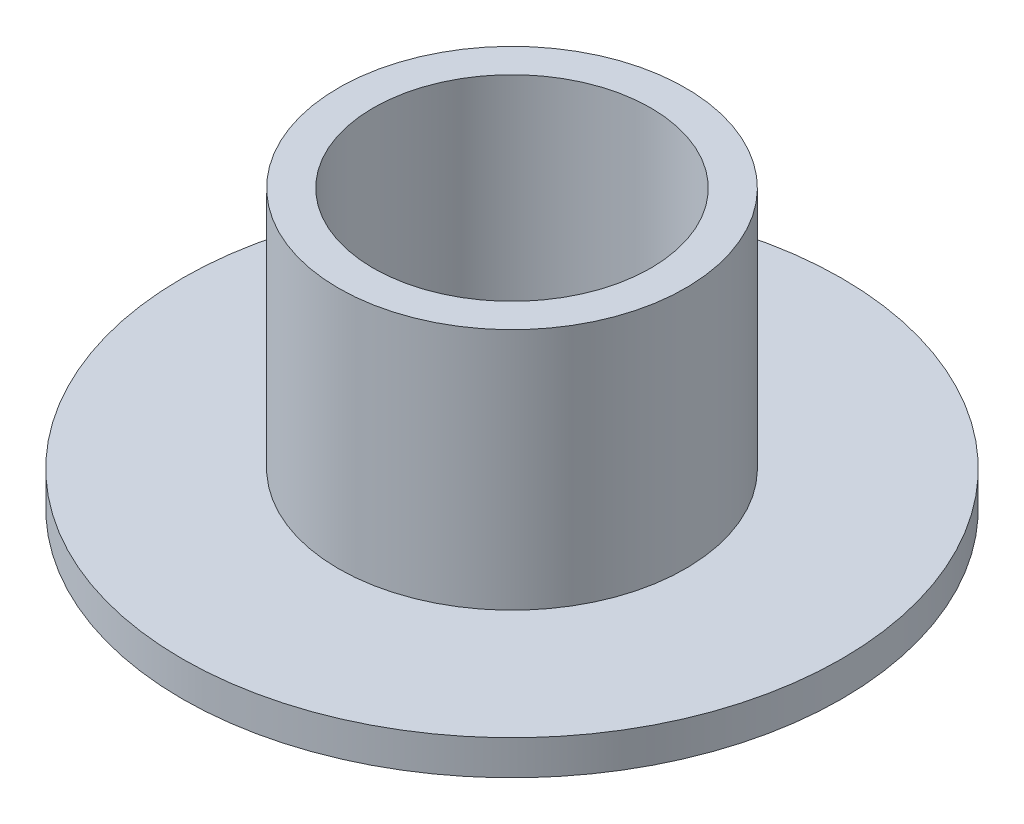
SolidWorks part; units mm, degrees
ref_plane "前视基准面" through (0, 0, 0) normal (0, 0, 1) x (1, 0, 0)
ref_plane "上视基准面" through (0, 0, 0) normal (0, 1, 0) x (1, 0, 0)
ref_plane "右视基准面" through (0, 0, 0) normal (1, 0, 0) x (0, 0, -1)
other "Configuration Table"
sketch "草图1" plane through (0, 0, 0) normal (0, 1, 0) x (1, 0, 0)
  circle A0 centre (0, 0) radius 4.75
  dimension "D1" = 9.5
extrude "凸台-拉伸1" add sketch "草图1" along normal blind 0.5
sketch "草图2" plane through (0, 0.5, 0) normal (0, 1, 0) x (1, 0, 0)
  circle A0 centre (0, 0) radius 2.5
  dimension "D1" = 5
extrude "凸台-拉伸2" add sketch "草图2" along normal blind 3.5
sketch "草图3" plane through (0, 0, 0) normal (0, -1, 0) x (1, 0, 0)
  circle A0 centre (0, 0) radius 2
  dimension "D1" = 4
extrude "切除-拉伸1" cut sketch "草图3" against normal through all
ref_axis "基准轴1" through (0, 9.1247, 0) along (0, -1, 0)
